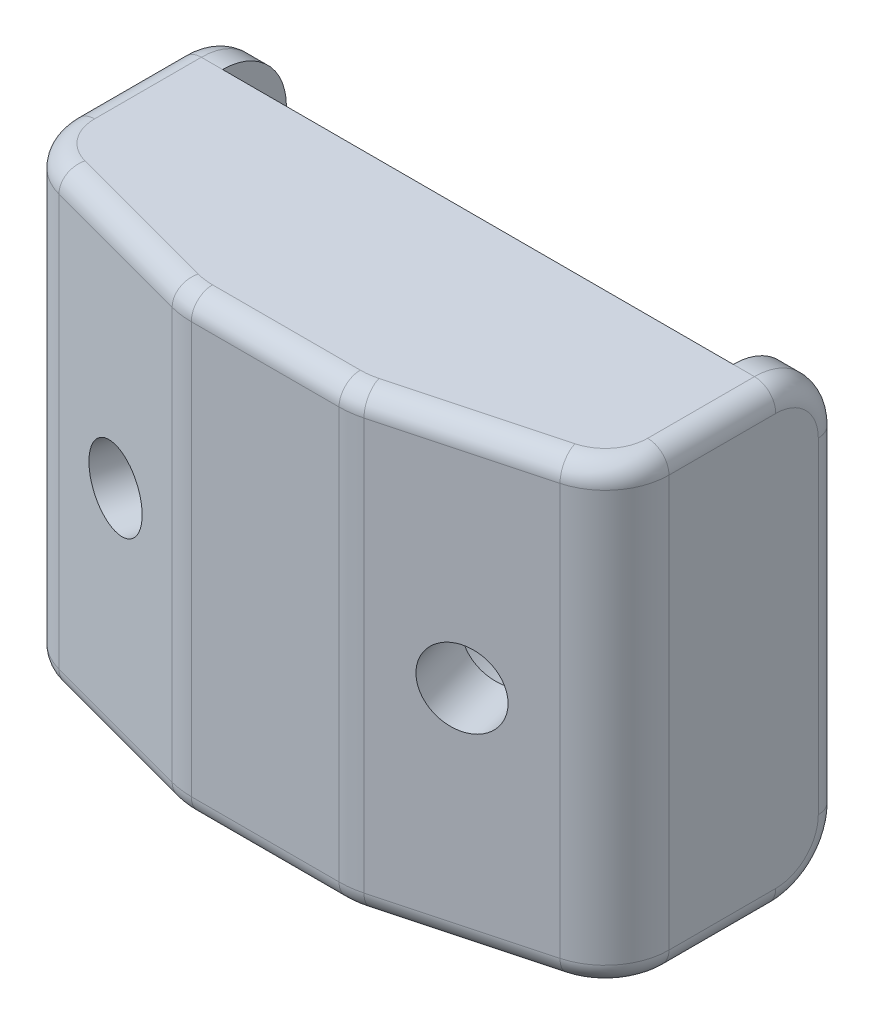
SolidWorks part; units mm, degrees
material "PET"
ref_plane "Front Plane" through (0, 0, 0) normal (0, 0, 1) x (1, 0, 0)
ref_plane "Top Plane" through (0, 0, 0) normal (0, 1, 0) x (1, 0, 0)
ref_plane "Right Plane" through (0, 0, 0) normal (1, 0, 0) x (0, 0, -1)
sketch "Sketch1" plane through (0, 0, 0) normal (0, 0, 1) x (1, 0, 0)
  line L8 (101.7795, 4.4787) -> (146.2295, 4.4787)
  line L9 (146.2295, 4.4787) -> (146.2295, 38.3463)
  line L10 (146.2295, 38.3463) -> (101.7795, 38.3463)
  line L11 (101.7795, 38.3463) -> (101.7795, 4.4787)
  line L20 (143.0545, 5.1137) -> (143.0545, 37.7113)
  line L21 (143.0545, 37.7113) -> (104.9545, 37.7113)
  line L22 (104.9545, 37.7113) -> (104.9545, 5.1137)
  line L23 (104.9545, 5.1137) -> (143.0545, 5.1137)
  dimension "D1" = 33.8676
  dimension "D2" = 44.45
  dimension "D3" = 3.175
  dimension "D4" = 3.175
extrude "Boss-Extrude1" add sketch "Sketch1" against normal blind 6.35
sketch "Sketch2" plane through (0, 0, 0) normal (0, 0, 1) x (1, 0, 0)
  line L4 (101.7795, 38.3463) -> (101.7795, 4.4787)
  line L5 (101.7795, 4.4787) -> (146.2295, 4.4787)
  line L6 (146.2295, 4.4787) -> (146.2295, 38.3463)
  line L7 (146.2295, 38.3463) -> (101.7795, 38.3463)
  line L8 (101.7795, 38.3463) -> (101.7795, 4.4787)
  line L9 (101.7795, 4.4787) -> (146.2295, 4.4787)
  line L10 (146.2295, 4.4787) -> (146.2295, 38.3463)
  line L11 (146.2295, 38.3463) -> (101.7795, 38.3463)
  dimension "D1" = 0
extrude "Boss-Extrude2" add sketch "Sketch2" along normal blind 9.525
sketch "Sketch3" plane through (0, 4.4787, 0) normal (0, -1, 0) x (1, 0, 0)
  line L0 (130.3545, 9.525) -> (146.2295, 5.2713)
  line L1 (101.7795, 9.525) -> (146.2295, 9.525) construction
  line L2 (146.2295, -6.35) -> (146.2295, 9.525) construction
  line L3 (146.2295, 5.2713) -> (146.2295, 9.525)
  line L4 (146.2295, 9.525) -> (130.3545, 9.525)
  line L5 (124.0045, 9.525) -> (124.0045, -6.35) construction
  line L6 (101.7795, -6.35) -> (146.2295, -6.35) construction
  line L7 (101.7795, 9.525) -> (117.6545, 9.525)
  line L8 (101.7795, 5.2713) -> (101.7795, 9.525)
  line L9 (117.6545, 9.525) -> (101.7795, 5.2713)
  dimension "D1" = 15
  dimension "D2" = 12.7
extrude "Cut-Extrude1" cut sketch "Sketch3" against normal through all
sketch "Sketch4" plane through (0, 0, -6.35) normal (0, 0, -1) x (-1, 0, 0)
  line L0 (-146.2295, 38.3463) -> (-101.7795, 38.3463) construction
  line L1 (-146.2295, 4.4787) -> (-143.0545, 4.4787)
  line L2 (-146.2295, 4.4787) -> (-146.2295, 38.3463)
  line L3 (-146.2295, 38.3463) -> (-143.0545, 38.3463)
  line L4 (-143.0545, 4.4787) -> (-143.0545, 38.3463)
  line L5 (-143.0545, 5.1137) -> (-143.0545, 37.7113) construction
  line L6 (-104.9545, 37.7113) -> (-104.9545, 5.1137) construction
  line L7 (-101.7795, 4.4787) -> (-104.9545, 4.4787)
  line L8 (-101.7795, 4.4787) -> (-101.7795, 38.3463)
  line L9 (-101.7795, 38.3463) -> (-104.9545, 38.3463)
  line L10 (-104.9545, 4.4787) -> (-104.9545, 38.3463)
extrude "Boss-Extrude3" add sketch "Sketch4" along normal blind 4.7625
shell "Shell2" thickness 4.7625 removed face at (124.0045, 21.4125, 0)
fillet "Fillet4" radius 4.7625 4 edges at (144.642, 38.3463, -11.1125) (103.367, 38.3463, -11.1125) (144.642, 4.4787, -11.1125) (103.367, 4.4787, -11.1125)
fillet "Fillet1" radius 4.7625 2 edges at (146.2295, 21.4125, 5.2713) (101.7795, 21.4125, 5.2713)
fillet "Fillet3" radius 6.35 2 edges at (117.6545, 21.4125, 9.525) (130.3545, 21.4125, 9.525)
fillet "Fillet2" radius 1.5875 24 edges at (124.0045, 38.3463, 9.525) (111.0781, 38.3463, 7.7629) (102.7636, 38.3463, 4.5161) (101.7795, 38.3463, -2.3665) (146.2295, 38.3463, -2.3665) (145.2453, 38.3463, 4.5161) (136.9308, 38.3463, 7.7629) (101.7795, 4.4787, -2.3665) (102.7636, 4.4787, 4.5161) (111.0781, 4.4787, 7.7629) (124.0045, 4.4787, 9.525) (136.9308, 4.4787, 7.7629) (145.2453, 4.4787, 4.5161) (146.2295, 4.4787, -2.3665) (130.3473, 38.3463, 9.4707) (117.6616, 38.3463, 9.4707) (130.3473, 4.4787, 9.4707) (117.6616, 4.4787, 9.4707) (101.7795, 5.8736, -9.7176) (101.7795, 21.4125, -11.1125) (101.7795, 36.9514, -9.7176) (146.2295, 36.9514, -9.7176) (146.2295, 21.4125, -11.1125) (146.2295, 5.8736, -9.7176)
hole_wizard "#10 Clearance Hole1" positions "Sketch5" profile "Sketch6" hole size "#10" standard "ANSI Inch" end condition up to next
sketch "Sketch5" plane through (5.5001, 0, -20.5267) normal (-0.2588, 0, 0.9659) x (0.9659, 0, 0.2588)
  line L0 (103.3301, 36.7588) -> (115.2747, 6.0662) construction
  point P7 (109.3024, 21.4125)
sketch "Sketch6" plane through (111.0781, 21.4125, 7.7629) normal (0, 1, 0) x (0.9659, 0, 0.2588)
  line L0 (0, 0) -> (0, 4.7625)
  line L1 (0, 4.7625) -> (2.8067, 4.7625)
  line L2 (2.8067, 4.7625) -> (2.8067, 0)
  line L5 (2.8067, 0) -> (0, 0)
  line L11 (0, -6.35) -> (0, 107.95) construction
  dimension "Thru Hole Dia." = 5.6134
  dimension "Thru Hole Depth" = 4.7625
ref_plane "Plane1" through (124.0045, 0, 0) normal (1, 0, 0) x (0, 0, -1)
mirror "Mirror1" about plane through (124.0045, 0, 0) normal (1, 0, 0) of "#10 Clearance Hole1"
ref_plane "Plane2" through (0, 21.4125, 0) normal (0, -1, 0) x (-1, 0, 0)
sketch "Sketch8" plane through (0, 5.1137, 0) normal (0, 1, 0) x (1, 0, 0)
  line L1 (106.542, 0) -> (106.542, -1.6169) construction
  line L2 (106.542, -1.6169) -> (118.2815, -4.7625) construction
  line L3 (118.2815, -4.7625) -> (129.7275, -4.7625) construction
  line L4 (129.7275, -4.7625) -> (141.467, -1.6169) construction
  line L5 (141.467, -1.6169) -> (141.467, 0) construction
  line L6 (104.9545, 0) -> (143.0545, 0) construction
  line L7 (143.0545, 0) -> (143.0545, 6.35) construction
  line L8 (143.0545, 6.35) -> (104.9545, 6.35) construction
  line L9 (104.9545, 6.35) -> (104.9545, 0) construction
  line L11 (106.542, 0) -> (106.542, -1.6169)
  line L12 (106.542, -1.6169) -> (118.2815, -4.7625)
  line L13 (118.2815, -4.7625) -> (129.7275, -4.7625)
  line L14 (129.7275, -4.7625) -> (141.467, -1.6169)
  line L15 (141.467, -1.6169) -> (141.467, 0)
  line L16 (104.9545, 0) -> (106.542, 0)
  line L17 (143.0545, 0) -> (143.0545, 6.35)
  line L18 (143.0545, 6.35) -> (104.9545, 6.35)
  line L19 (104.9545, 6.35) -> (104.9545, 0)
  line L20 (141.467, 0) -> (143.0545, 0)
extrude "Boss-Extrude4" add sketch "Sketch8" along normal up to next
sketch "Sketch9" plane through (5.5001, 0, -20.5267) normal (-0.2588, 0, 0.9659) x (0.9659, 0, 0.2588)
  circle A0 centre (109.3024, 21.4125) radius 5.5562 construction
  circle A1 centre (109.3024, 21.4125) radius 5.5563 construction
  circle A2 centre (109.3024, 21.4125) radius 6.8262
  dimension "D1" = 1.27
extrude "Cut-Extrude2" cut sketch "Sketch9" against normal through all from offset 4.7625 offset against normal yes
mirror "Mirror2" about plane through (124.0045, 0, 0) normal (1, 0, 0) of "Cut-Extrude2"
hole_wizard "Hole1" positions "Sketch11" profile "Sketch12" legacy
sketch "Sketch11" plane through (0, 0, -6.35) normal (0, 0, -1) x (-1, 0, 0)
  line L2 (-124.0045, 21.4125) -> (-124.0045, 4.4787) construction
  line L3 (-104.9545, 4.4787) -> (-143.0545, 4.4787) construction
  line L4 (-114.8597, 21.4125) -> (-133.1492, 21.4125) construction
  ellipse E3 centre (-133.1492, 21.4125) end of major axis (-140.2163, 21.4125) minor radius 6.8262 construction
  ellipse E4 centre (-114.8597, 21.4125) end of major axis (-107.7926, 21.4125) minor radius 6.8262 construction
  point P53 (-124.0045, 11.2525)
  point P55 (-124.0045, 31.5725)
  dimension "D1" = 10.16
sketch "Sketch12" plane through (124.0045, 31.5725, -6.35) normal (1, 0, 0) x (0, 1, 0)
  line L0 (0, 0) -> (0, 7.62)
  line L1 (0, 7.62) -> (4.4323, 7.62)
  line L2 (4.4323, 7.62) -> (4.6101, 0)
  line L3 (4.6101, 0) -> (0, 0)
  line L4 (0, 110) -> (0, -10) construction
  dimension "Minor Diameter" = 8.8646
  dimension "Depth" = 7.62
  dimension "Major Diameter" = 9.2202
hole_wizard "1/4 Clearance Hole1" positions "Sketch13" profile "Sketch14" hole size "1/4" standard "ANSI Inch"
sketch "Sketch13" plane through (0, 0, -6.35) normal (0, 0, -1) x (-1, 0, 0)
  point P0 (-124.0045, 11.2525)
  point P3 (-124.0045, 31.5725)
sketch "Sketch14" plane through (124.0045, 11.2525, -6.35) normal (1, 0, 0) x (0, 1, 0)
  line L0 (0, 0) -> (0, 11.7978)
  line L1 (0, 11.7978) -> (3.5712, 9.652)
  line L2 (3.5712, 9.652) -> (3.5712, 0)
  line L5 (3.5712, 0) -> (0, 0)
  line L10 (0, 11.7978) -> (-3.5712, 9.652) construction
  line L11 (0, -6.35) -> (0, 107.95) construction
  dimension "Hole Dia." = 7.1425
  dimension "Hole Depth" = 9.652
  dimension "Drill Angle" = 118
